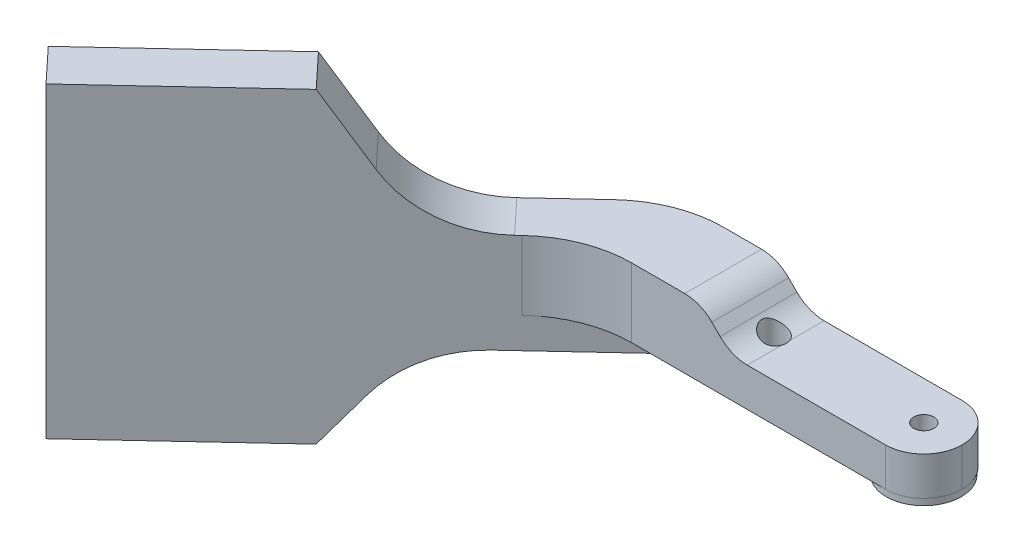
SolidWorks part; units mm, degrees
ref_plane "Front" through (0, 0, 0) normal (0, 0, 1) x (1, 0, 0)
ref_plane "Top" through (0, 0, 0) normal (0, 1, 0) x (1, 0, 0)
ref_plane "Right" through (0, 0, 0) normal (1, 0, 0) x (0, 0, -1)
sketch "Sketch1" plane through (0, 0, 0) normal (0, 1, 0) x (1, 0, 0)
  line L0 (0, 10) -> (0, 0)
  line L1 (0, 0) -> (42, 0)
  line L3 (0, 10) -> (42, 10)
  line L4 (42, 0) -> (42, 10)
  line L9 (0, 10) -> (-42.4185, -29.5559)
  line L10 (-42.4185, -29.5559) -> (-38.3265, -33.944)
  line L11 (0, 10) -> (4.092, 5.6119)
  line L12 (-38.3265, -33.944) -> (4.092, 5.6119)
  line L13 (0, 0) -> (-1.926, 0)
  line L14 (-1.926, 0) -> (0, 1.796)
  line L15 (0, 1.796) -> (0, 0)
  dimension "D1" = 10
  dimension "D2" = 42
  dimension "D3" = 223
  dimension "D4" = 58
  dimension "D5" = 6
  dimension "D6" = 270
extrude "Boss-Extrude1" add sketch "Sketch1" along normal blind 5 contours L10 L12 L1 L0 L9 | L1 L12 L11 L0 | L12 L1 L4 L3 L11 | L13 L0 L12
fillet "Fillet1" radius 5 2 edges at (42, 2.5, 0) (42, 2.5, -10)
sketch "Sketch2" plane through (0, 5, 0) normal (0, 1, 0) x (1, 0, 0)
  circle A0 centre (37, 5) radius 1.3
extrude "Cut-Extrude1" cut sketch "Sketch2" against normal blind 10
sketch "Sketch3" plane through (0, 5, 0) normal (0, 1, 0) x (1, 0, 0)
  line L0 (-42.4185, -29.5559) -> (-38.3265, -33.944)
  line L1 (-38.3265, -33.944) -> (-20.1263, -16.972)
  line L2 (-38.3265, -33.944) -> (-1.926, 0) construction
  line L3 (-20.1263, -16.972) -> (-24.2183, -12.5839)
  line L4 (0, 10) -> (-42.4185, -29.5559) construction
  line L5 (-24.2183, -12.5839) -> (-42.4185, -29.5559)
extrude "Boss-Extrude2" add sketch "Sketch3" along normal blind 20
sketch "Sketch4" plane through (0, 0, 0) normal (0, -1, 0) x (1, 0, 0)
  line L0 (-42.4185, 29.5559) -> (-38.3265, 33.944)
  line L1 (-38.3265, 33.944) -> (-20.1263, 16.972)
  line L2 (-38.3265, 33.944) -> (-1.926, 0) construction
  line L3 (-20.1263, 16.972) -> (-24.2183, 12.5839)
  line L4 (0, -10) -> (-42.4185, 29.5559) construction
  line L5 (-24.2183, 12.5839) -> (-42.4185, 29.5559)
extrude "Boss-Extrude3" add sketch "Sketch4" along normal blind 15
sketch "Sketch5" plane through (-4.9878, 0, -5.3488) normal (-0.682, 0, -0.7314) x (-0.7314, 0, 0.682)
  line L0 (26.2943, -15) -> (26.2943, 0)
  line L1 (26.2943, 0) -> (13.889, 0)
  line L2 (-6.82, 0) -> (26.2943, 0) construction
  line L3 (13.889, 0) -> (26.2943, -15)
  line L4 (13.889, 5) -> (26.2943, 25)
  line L5 (-6.82, 5) -> (26.2943, 5) construction
  line L6 (26.2943, 25) -> (26.2943, 5)
  line L7 (26.2943, 5) -> (13.889, 5)
extrude "Boss-Extrude4" add sketch "Sketch5" against normal blind 6
sketch "Sketch6" plane through (0, 0, 0) normal (0, -1, 0) x (1, 0, 0)
  circle A0 centre (37, -5) radius 4.9
  circle A1 centre (37, -5) radius 1.3
extrude "Boss-Extrude5" add sketch "Sketch6" along normal blind 0.9
sketch "Sketch8" plane through (0, 0, 0) normal (0, -1, 0) x (1, 0, 0)
  line L0 (0, -10) -> (-19.6819, 8.3537)
  line L1 (-24.2183, 12.5839) -> (-15.1456, 4.1235) construction
  line L6 (-19.6819, 8.3537) -> (-15.5899, 12.7418)
  line L7 (-20.1263, 16.972) -> (-11.0536, 8.5116) construction
  line L8 (-15.5899, 12.7418) -> (8.7977, -10)
  line L9 (0, -10) -> (37, -10) construction
  line L10 (8.7977, -10) -> (0, -10)
extrude "Boss-Extrude6" add sketch "Sketch8" along normal blind 4
sketch "Sketch9" plane through (0, 5, 0) normal (0, 1, 0) x (1, 0, 0)
  line L3 (-17.565, -6.3796) -> (-24.2183, -12.5839) construction
  line L4 (-20.8916, -9.4817) -> (0, 10)
  line L6 (-20.8916, -9.4817) -> (-16.7996, -13.8699)
  line L7 (-20.1263, -16.972) -> (-11.0536, -8.5116) construction
  line L9 (-16.7996, -13.8699) -> (8.7977, 10)
  line L10 (0, 10) -> (37, 10) construction
  line L11 (8.7977, 10) -> (0, 10)
  line L12 (37, 0) -> (-1.926, 0) construction
  line L13 (8.7977, 0) -> (-1.926, 0)
  line L14 (-1.926, 0) -> (8.7977, 10)
  line L15 (8.7977, 10) -> (17.9505, 10)
  line L16 (17.9505, 10) -> (17.9505, 0)
  line L17 (17.9505, 0) -> (8.7977, 0)
extrude "Boss-Extrude7" add sketch "Sketch9" along normal blind 4
fillet "Fillet2" radius 15 4 edges at (-15.519, -4, 8.5736) (-14.9141, 9, 8.0096) (-1.926, 4.5, 0) (0, 2.5, -10)
fillet "Fillet7" radius 5 1 edges at (17.9505, 9, -5) profile chamfer
fillet "Fillet8" radius 5 2 edges at (12.9505, 9, -5) (16.9505, 5, -5)
sketch "Sketch10" plane through (0, 0, 0) normal (0, -1, 0) x (-1, 0, 0)
  circle A0 centre (-17.5, 5) radius 1.6
extrude "Cut-Extrude2" cut sketch "Sketch10" against normal blind 10
